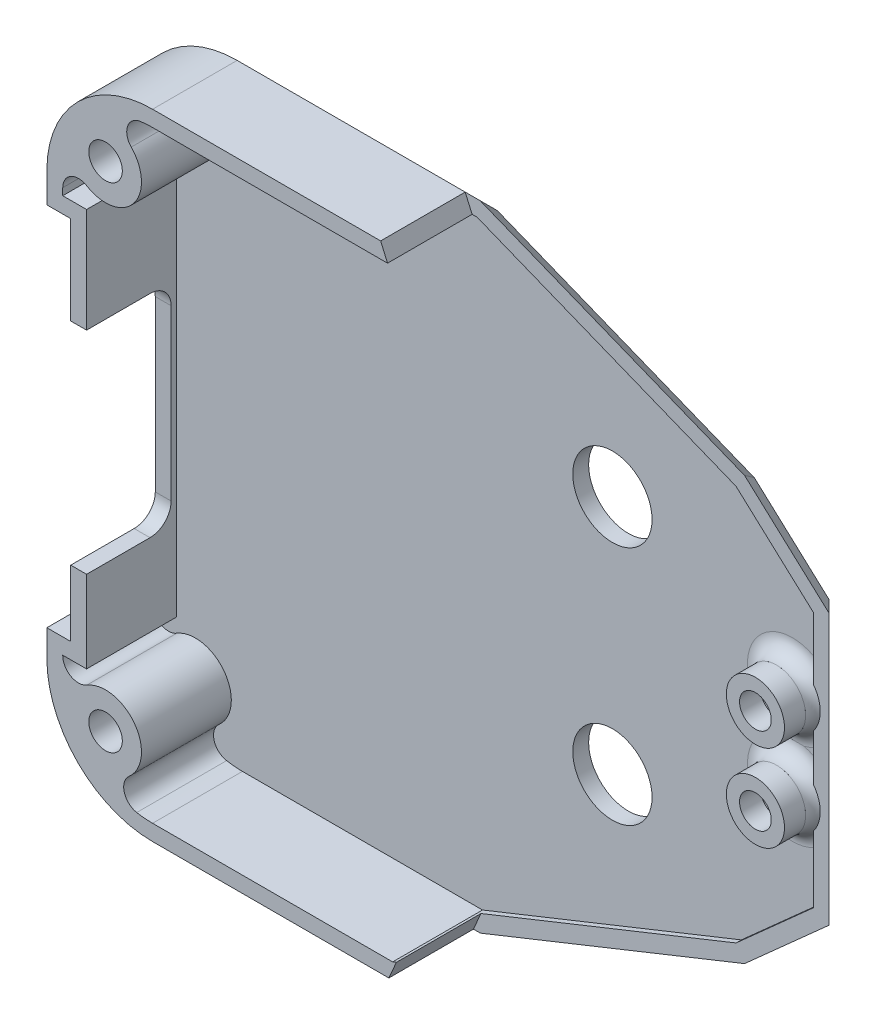
SolidWorks part; units mm, degrees
ref_plane "Front Plane" through (0, 0, 0) normal (0, 0, 1) x (1, 0, 0)
ref_plane "Top Plane" through (0, 0, 0) normal (0, 1, 0) x (1, 0, 0)
ref_plane "Right Plane" through (0, 0, 0) normal (1, 0, 0) x (0, 0, -1)
sketch "Sketch1" plane through (0, 0, 0) normal (0, 0, 1) x (1, 0, 0)
  line L24 (-34.4979, 18.0565) -> (-34.4979, -16.5845)
  line L25 (-34.4979, -16.5845) -> (-36.7534, -16.5845)
  line L26 (-36.7534, -16.5845) -> (-36.7534, -19.1061)
  line L27 (-26.7534, -29.1061) -> (-3.7534, -29.1061)
  line L28 (-3.7534, -29.1061) -> (21.2466, -19.1061)
  line L29 (21.2466, -19.1061) -> (29.2466, -11.9575)
  line L30 (29.2466, -11.9575) -> (29.2466, 13.5964)
  line L31 (29.2466, 13.5964) -> (21.2466, 20.8939)
  line L32 (21.2466, 20.8939) -> (-3.7534, 30.8939)
  line L33 (-3.7534, 30.8939) -> (-26.7534, 30.8939)
  line L34 (-36.7534, 20.8939) -> (-36.7534, 18.0565)
  line L35 (-36.7534, 18.0565) -> (-34.4979, 18.0565)
  arc A4 (-36.7534, -19.1061) -> (-26.7534, -29.1061) centre (-26.7534, -19.1061) ccw
  arc A5 (-26.7534, 30.8939) -> (-36.7534, 20.8939) centre (-26.7534, 20.8939) ccw
extrude "Boss-Extrude1" add sketch "Sketch1" along normal blind 10 contours L24 L25 L26 A4 L27 L28 L29 L30 L31 L32 L33 A5 L34 L35
shell "Shell1" thickness 1.5 removed face at (-12.8699, 0.8382, 10)
chamfer "Chamfer1" distance 2 angle 45 14 edges at (-34.4979, 0.736, 0) (-35.6256, -16.5845, 0) (-36.7534, -17.8453, 0) (-33.8245, -26.1771, 0) (-15.2534, -29.1061, 0) (8.7466, -24.1061, 0) (25.2466, -15.5318, 0) (29.2466, 0.8195, 0) (25.2466, 17.2452, 0) (8.7466, 25.8939, 0) (-15.2534, 30.8939, 0) (-33.8245, 27.965, 0) (-36.7534, 19.4752, 0) (-35.6256, 18.0565, 0)
sketch "Sketch2" plane through (0, 0, 0) normal (0, 0, -1) x (-1, 0, 0)
  line L2 (-8.2466, 0) -> (7.2739, -35.7146)
  line L3 (0, 0) -> (-115.6033, 0) construction
  line L4 (-8.2466, 0) -> (-42.1518, 0)
  line L5 (-8.2466, 0) -> (7.2739, 35.7146)
  arc A1 (-42.1518, 0) -> (7.2739, 35.7146) centre (20.4615, -34.5935) cw
  arc A2 (-42.1518, 0) -> (7.2739, -35.7146) centre (20.4615, 34.5935) ccw
  line M10 (26.7534, 28.8939) -> (4.1386, 28.8939)
  line M11 (4.1386, 28.8939) -> (-20.1669, 19.1718)
  line M12 (-20.1669, 19.1718) -> (-27.2466, 12.7137)
  line M13 (-27.2466, 12.7137) -> (-27.2466, -11.0625)
  line M14 (-27.2466, -11.0625) -> (-20.1767, -17.38)
  line M15 (-20.1767, -17.38) -> (4.1386, -27.1061)
extrude "Cut-Extrude4" cut sketch "Sketch2" against normal blind 10 from offset 2 contours L4 L5 M10 M11 M12 M13 | L2 L4 M13 M14 M15 | L4 A2 L2 M15 M14 M13 | A1 L4 L5 M13 M12 M11 M10 region at (13.3546, -11.1191, 0) region at (13.1653, 12.2011, 0) region at (18.6179, -18.2248, 0) region at (34.6992, 0.6098, 0) offset against normal yes
sketch "Sketch3" plane through (0, 0, 0) normal (0, 0, -1) x (-1, 0, 0)
  line L0 (-25.2728, -3.0797) -> (-25.2728, 5.1176) construction
  line L3 (-25.2728, 1.0189) -> (-32.7428, 1.0189) construction
  circle A6 centre (-25.2728, -3.0797) radius 1.5
  circle A10 centre (-25.2728, -3.0797) radius 2.75
  circle A11 centre (-25.2728, 5.1176) radius 2.75
  circle A12 centre (-25.2728, 5.1176) radius 1.5
  dimension "D1" = 5.5
extrude "Boss-Extrude2" add sketch "Sketch3" against normal blind 3.5 from surface starting at face at (-12.5534, 0.839, 1.5)
sketch "Sketch4" plane through (0, 0, 1.5) normal (0, 0, 1) x (1, 0, 0)
  circle A0 centre (25.2728, 5.1176) radius 1.5
  circle A1 centre (25.2728, -3.0797) radius 1.5
extrude "Cut-Extrude5" cut sketch "Sketch4" against normal through all
fillet "Fillet1" radius 1.5 2 edges at (22.5228, 5.1176, 1.5) (22.5228, -3.0797, 1.5)
sketch "Sketch5" plane through (0, 0, 0) normal (0, 0, -1) x (-1, 0, 0)
  circle A0 centre (-25.2728, 5.1176) radius 2.75
  circle A1 centre (-25.2728, -3.0797) radius 2.75
  dimension "D1" = 5.5
extrude "Cut-Extrude6" cut sketch "Sketch5" against normal blind 3
sketch "Sketch6" plane through (0, 0, 0) normal (0, 0, -1) x (-1, 0, 0)
  circle A0 centre (31.204, -22.2994) radius 1.5875
  circle A1 centre (31.204, -22.2994) radius 2.75
  circle A2 centre (31.204, 24.4031) radius 2.75
  circle A3 centre (31.204, 24.4031) radius 1.5875
  dimension "D1" = 3.175
  dimension "D2" = 5.5
extrude "Cut-Extrude7" cut sketch "Sketch6" against normal through all contours A3 | A0 region at (-31.204, -22.2994, 0) region at (-31.204, 24.4031, 0)
extrude "Cut-Extrude8" cut sketch "Sketch6<3>" against normal blind 3
sketch "Sketch6<3>" plane through (0, 0, 0) normal (0, 0, -1) x (-1, 0, 0) same geometry as "Sketch6"
sketch "Sketch7" plane through (0, 0, 1.5) normal (0, 0, 1) x (1, 0, 0)
  line L0 (-33.7534, 1.0519) -> (-49.9933, 1.0519) construction
  circle A0 centre (-31.204, -22.2994) radius 3.4
  circle A1 centre (-31.204, 24.4031) radius 3.4
  circle A2 centre (-31.204, -22.2994) radius 1.5875
  circle A3 centre (-31.204, 24.4031) radius 1.5875
  dimension "D1" = 6.8
extrude "Boss-Extrude3" add sketch "Sketch7" along normal up to surface (8.5 mm away) up to face at (-26.6445, -0.5166, 10)
fillet "Fillet2" radius 1.5 4 edges at (-34.5961, 24.1714, 5.75) (-31.77, 27.7557, 5.75) (-34.6034, -22.3662, 5.75) (-32.3561, -25.4982, 5.75)
sketch "Sketch8" plane through (0, 0, 0) normal (0, 0, -1) x (-1, 0, 0)
  circle A0 centre (-8.2466, 12.3939) radius 3.75
  circle A1 centre (-8.2466, -10.3561) radius 3.75
  dimension "D1" = 7.5
extrude "Cut-Extrude9" cut sketch "Sketch8" against normal blind 10
sketch "Sketch9" plane through (-34.4979, 0, 0) normal (-1, 0, 0) x (0, 0, 1)
  line L0 (10, 18.0565) -> (10, -16.5845) construction
  line L1 (10, 9.6703) -> (2, 9.6703)
  line L2 (10, 9.6703) -> (10, -10.3297)
  line L3 (10, -10.3297) -> (2, -10.3297)
  line L4 (2, 9.6703) -> (2, -10.3297)
  line L5 (2, 18.0565) -> (2, -16.5845) construction
  dimension "D2" = 20
  dimension "D3" = 10
extrude "Cut-Extrude10" cut sketch "Sketch9" against normal blind 10
fillet "Fillet3" radius 2 2 edges at (-33.7479, -10.3297, 2) (-33.7479, 9.6703, 2)
